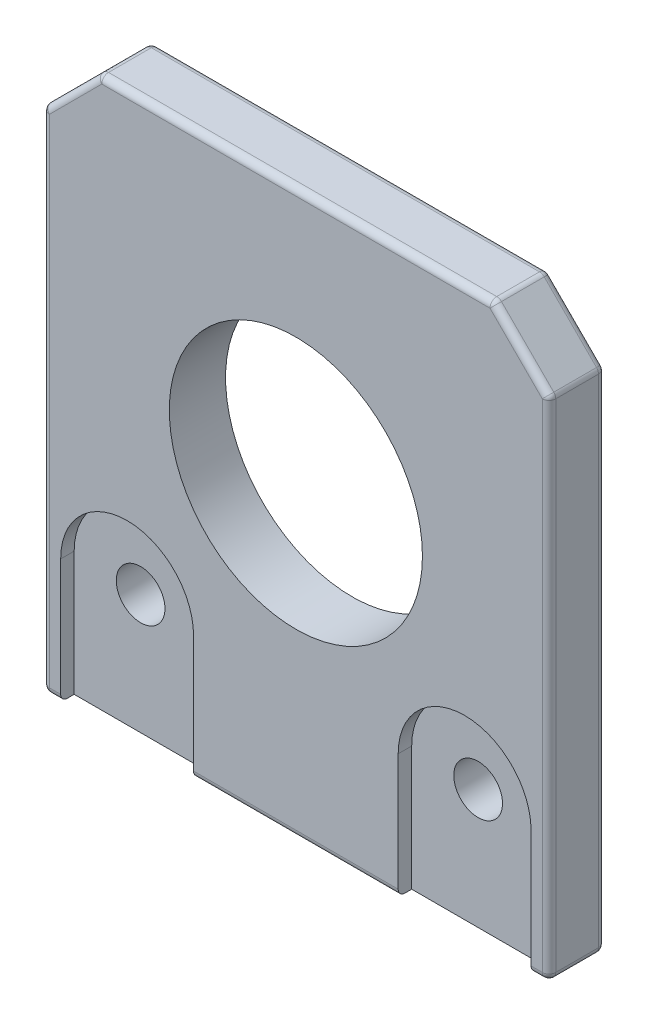
SolidWorks part; units mm, degrees
ref_plane "Front Plane" through (0, 0, 0) normal (0, 0, 1) x (1, 0, 0)
ref_plane "Top Plane" through (0, 0, 0) normal (0, 1, 0) x (1, 0, 0)
ref_plane "Right Plane" through (0, 0, 0) normal (1, 0, 0) x (0, 0, -1)
sketch "Sketch2" plane through (0, 0, 0) normal (0, 1, 0) x (1, 0, 0)
  line L1 (-28.575, 3.175) -> (28.575, 3.175)
  line L2 (-28.575, 3.175) -> (-28.575, -3.175)
  line L3 (-28.575, -3.175) -> (28.575, -3.175)
  line L4 (28.575, 3.175) -> (28.575, -3.175)
  point P4 (0, 3.175)
  point P7 (-28.575, 0)
  dimension "D1" = 6.35
  dimension "D2" = 57.15
extrude "Boss-Extrude1" add sketch "Sketch2" against normal blind 63.5
sketch "Sketch3" plane through (0, 0, 3.175) normal (0, 0, 1) x (1, 0, 0)
  line L2 (-28.575, 0) -> (28.575, 0) construction
  circle A0 centre (0, -28.815) radius 14.2875
  point P2 (0, 0)
  dimension "D1" = 28.815
  dimension "D3" = 28.575
extrude "Cut-Extrude1" cut sketch "Sketch3" against normal through all
chamfer "Chamfer1" distance 6.35 angle 45 2 edges at (-28.575, 0, 0) (28.575, 0, 0)
hole_wizard "M4 Clearance Hole1" positions "Sketch4" profile "Sketch5" hole size "M4" standard "ANSI Metric" rebuild error yes end condition through all
sketch "Sketch4" plane through (0, 0, -3.175) normal (0, 0, -1) x (-1, 0, 0)
  point P0 (-29.5299, -95.5505)
sketch "Sketch5" plane through (29.5299, -95.5505, -3.175) normal (1, 0, 0) x (0, 1, 0)
  line L0 (0, 0) -> (0, 6.35)
  line L1 (0, 6.35) -> (2.25, 6.35)
  line L2 (2.25, 6.35) -> (2.25, 0)
  line L5 (2.25, 0) -> (0, 0)
  line L11 (0, -6.35) -> (0, 107.95) construction
  dimension "Thru Hole Dia." = 4.5
  dimension "Thru Hole Depth" = 6.35
hole_wizard "M5 Clearance Hole1" positions "Sketch6" profile "Sketch7" hole size "M5" standard "ANSI Metric" end condition through all
sketch "Sketch6" plane through (0, 0, 3.175) normal (0, 0, 1) x (1, 0, 0)
  line L0 (-28.575, -63.5) -> (28.575, -63.5) construction
  line L1 (28.575, -63.5) -> (28.575, -6.35) construction
  point P0 (-19.05, -50)
  point P3 (19.05, -50)
  dimension "D1" = 13.5
  dimension "D2" = 9.525
  dimension "D3" = 38.1
sketch "Sketch7" plane through (-19.05, -50, 3.175) normal (1, 0, 0) x (0, -1, 0)
  line L0 (0, 0) -> (0, 6.35)
  line L1 (0, 6.35) -> (2.75, 6.35)
  line L2 (2.75, 6.35) -> (2.75, 0)
  line L5 (2.75, 0) -> (0, 0)
  line L11 (0, -6.35) -> (0, 107.95) construction
  dimension "Thru Hole Dia." = 5.5
  dimension "Thru Hole Depth" = 6.35
fillet "Fillet1" radius 0.762 18 edges at (0, -63.5, 3.175) (0, -63.5, -3.175) (28.575, -63.5, 0) (28.575, -34.925, 3.175) (28.575, -34.925, -3.175) (-28.575, -63.5, 0) (-28.575, -34.925, -3.175) (-28.575, -34.925, 3.175) (-25.4, -3.175, 3.175) (-28.575, -6.35, 0) (-25.4, -3.175, -3.175) (0, 0, 3.175) (-22.225, 0, 0) (0, 0, -3.175) (22.225, 0, 0) (25.4, -3.175, -3.175) (28.575, -6.35, 0) (25.4, -3.175, 3.175)
sketch "Sketch8" plane through (0, 0, 3.175) normal (0, 0, 1) x (1, 0, 0)
  line L0 (11.55, -63.5) -> (11.55, -49.5)
  line L1 (26.55, -49.5) -> (26.55, -63.5)
  line L2 (11.55, -63.5) -> (26.55, -63.5)
  arc A0 (11.55, -49.5) -> (26.55, -49.5) centre (19.05, -49.5) cw
extrude "Cut-Extrude4" cut sketch "Sketch8" against normal blind 1.524
mirror "Mirror1" about plane through (0, 0, 0) normal (1, 0, 0) of "Cut-Extrude4"
